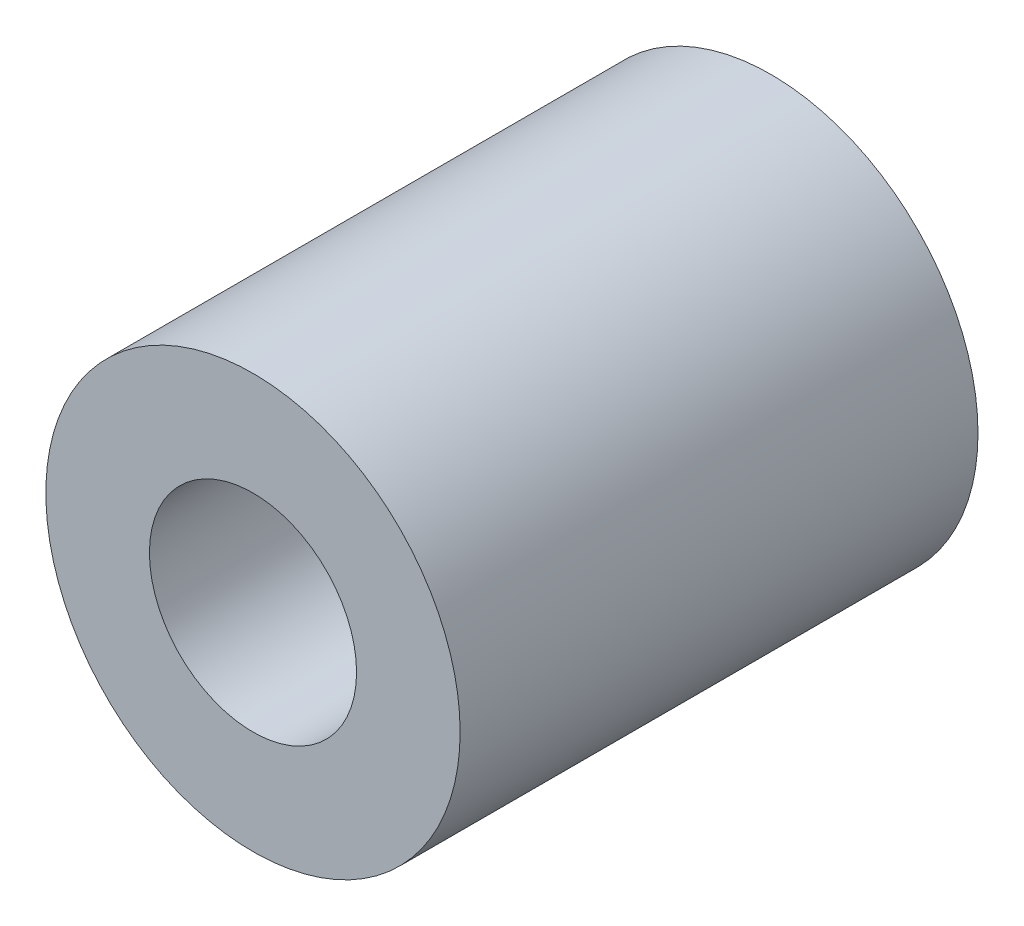
SolidWorks part; units mm, degrees
ref_plane "Front Plane" through (0, 0, 0) normal (0, 0, 1) x (1, 0, 0)
ref_plane "Top Plane" through (0, 0, 0) normal (0, 1, 0) x (1, 0, 0)
ref_plane "Right Plane" through (0, 0, 0) normal (1, 0, 0) x (0, 0, -1)
sketch "Sketch1" plane through (0, 0, 0) normal (0, 0, 1) x (1, 0, 0)
  circle A0 centre (0, 0) radius 6.35
  circle A1 centre (0, 0) radius 3.175
  dimension "D1" = 6.35
  dimension "D2" = 12.7
extrude "Boss-Extrude1" add sketch "Sketch1" along normal mid plane 15.875
